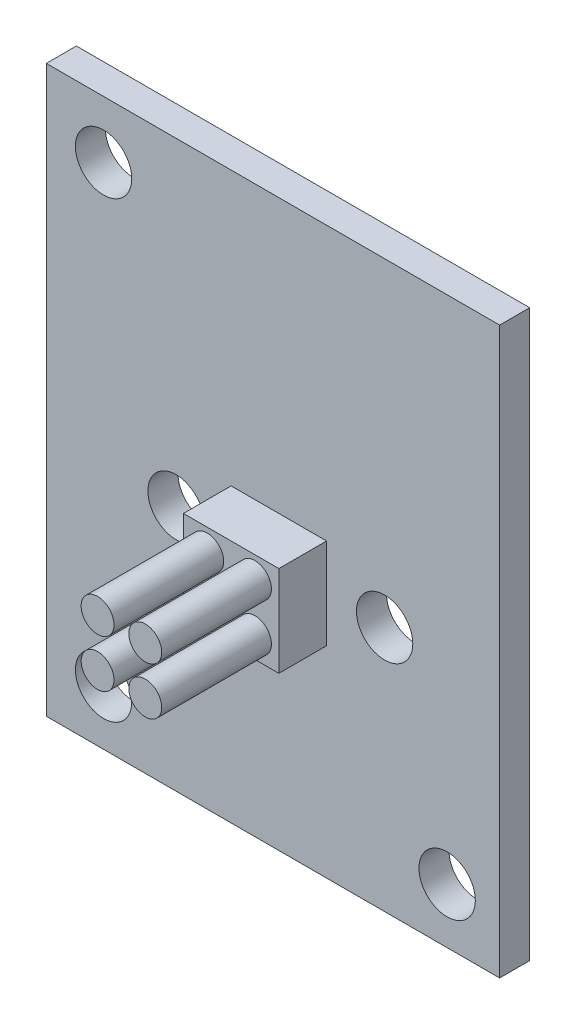
SolidWorks part; units mm, degrees
ref_plane "Front Plane" through (0, 0, 0) normal (0, 0, 1) x (1, 0, 0)
ref_plane "Top Plane" through (0, 0, 0) normal (0, 1, 0) x (1, 0, 0)
ref_plane "Right Plane" through (0, 0, 0) normal (1, 0, 0) x (0, 0, -1)
sketch "Sketch1" plane through (0, 0, 0) normal (0, 0, 1) x (1, 0, 0)
  line L0 (12.065, 30.099) -> (12.065, 35.0132) construction
  line L1 (0, 0) -> (24.13, 0)
  line L2 (0, 0) -> (0, 30.099)
  line L3 (0, 30.099) -> (24.13, 30.099)
  line L4 (24.13, 0) -> (24.13, 30.099)
  line L5 (-4.9142, -4.9142) -> (29.0442, -4.9142) construction
  line L6 (-4.9142, -4.9142) -> (-4.9142, 35.0132) construction
  line L7 (-4.9142, 35.0132) -> (29.0442, 35.0132) construction
  line L8 (29.0442, -4.9142) -> (29.0442, 35.0132) construction
  line L9 (12.065, -4.9142) -> (12.065, 0) construction
  line L10 (-4.9142, 15.0495) -> (0, 15.0495) construction
  line L11 (29.0442, 15.0495) -> (24.13, 15.0495) construction
  line L12 (0, 0) -> (-4.9142, 0) construction
  line L13 (0, 0) -> (0, -4.9142) construction
  line L14 (-4.9142, -4.9142) -> (-3.9749, -3.9749) construction
  line L15 (-1.5, 15.0495) -> (0, 15.0495) construction
  line L16 (-1.8536, -1.8536) -> (-3.9749, -3.9749) construction
  line L17 (-4.4142, -2.9142) -> (-4.9142, -2.9142) construction
  line L18 (-1.5, -1.5) -> (25.63, -1.5) construction
  line L19 (-1.5, -1.5) -> (-1.5, 31.599) construction
  line L20 (-1.5, 31.599) -> (25.63, 31.599) construction
  line L21 (25.63, -1.5) -> (25.63, 31.599) construction
  line L22 (25.63, 15.0495) -> (24.13, 15.0495) construction
  line L23 (12.065, 31.599) -> (12.065, 30.099) construction
  line L24 (12.065, -1.5) -> (12.065, 0) construction
  line L25 (-1.8536, -1.8536) -> (-1.5, -1.5)
  line L26 (13.6479, 14.3949) -> (11.1079, 11.8549) construction
  line L27 (11.1079, 11.8549) -> (13.6479, 11.8549) construction
  line L28 (11.1079, 11.8549) -> (11.1079, 14.3949) construction
  line L29 (11.1079, 14.3949) -> (13.6479, 14.3949) construction
  line L30 (13.6479, 11.8549) -> (13.6479, 14.3949) construction
  line L31 (11.1079, 14.3949) -> (13.6479, 11.8549) construction
  line L32 (14.9179, 15.5399) -> (9.8379, 10.7099) construction
  line L33 (14.9179, 10.7099) -> (9.8379, 10.7099)
  line L34 (14.9179, 10.7099) -> (14.9179, 15.5399)
  line L35 (14.9179, 15.5399) -> (9.8379, 15.5399)
  line L36 (9.8379, 10.7099) -> (9.8379, 15.5399)
  line L37 (9.8379, 15.5399) -> (14.9179, 10.7099) construction
  line L39 (5.842, 16.256) -> (23.622, 16.256)
  line L40 (5.842, 16.256) -> (5.842, 29.591)
  line L41 (5.842, 29.591) -> (23.622, 29.591)
  line L42 (23.622, 16.256) -> (23.622, 29.591)
  circle A0 centre (3.048, 2.921) radius 1.5
  circle A1 centre (21.336, 2.921) radius 1.5
  circle A2 centre (3.048, 27.051) radius 1.5
  circle A3 centre (6.908, 13.095) radius 1.5
  circle A4 centre (18.0081, 13.095) radius 1.5
  circle A5 centre (-2.9142, -2.9142) radius 1.5 construction
  circle A6 centre (27.0442, -2.9142) radius 1.5 construction
  circle A7 centre (-2.9142, 33.0132) radius 1.5 construction
  circle A8 centre (27.0442, 33.0132) radius 1.5 construction
  circle A9 centre (3.048, 2.921) radius 2 construction
  circle A10 centre (6.908, 13.095) radius 2 construction
  circle A11 centre (18.0081, 13.095) radius 2 construction
  circle A12 centre (21.336, 2.921) radius 2 construction
  circle A13 centre (3.048, 27.051) radius 2 construction
  circle A14 centre (11.1079, 14.3949) radius 0.875
  circle A15 centre (13.6479, 14.3949) radius 0.875
  circle A16 centre (11.1079, 11.8549) radius 0.875
  circle A17 centre (13.6479, 11.8549) radius 0.875
  circle A18 centre (12.3779, 13.1249) radius 3.5 construction
  circle A19 centre (12.3779, 13.1249) radius 3 construction
  arc A20 (8.8874, 13.3818) -> (8.8904, 12.8299) centre (12.3779, 13.1249) cw construction
  point P71 (12.3779, 13.1249)
  dimension "D5" = 3
  dimension "D10" = 3
  dimension "D13" = 3
  dimension "D16" = 3
  dimension "D17" = 3
  dimension "D20" = 4
  dimension "D25" = 1.75
  dimension "D26" = 7
  dimension "D27" = 0.5
  dimension "D1" = 24.13
  dimension "D2" = 30.099
  dimension "D3" = 3.048
  dimension "D4" = 2.921
  dimension "D6" = 21.336
  dimension "D7" = 2.921
  dimension "D8" = 3.048
  dimension "D9" = 27.051
  dimension "D11" = 13.095
  dimension "D12" = 6.908
  dimension "D14" = 18.0081
  dimension "D15" = 13.095
  dimension "D18" = 0.5
  dimension "D19" = 1.5
  dimension "D21" = 11.1079
  dimension "D22" = 11.8549
  dimension "D23" = 13.6479
  dimension "D24" = 14.3949
  dimension "D28" = 4.83
  dimension "D29" = 5.08
  dimension "D30" = 16.256
  dimension "D31" = 5.842
  dimension "D32" = 17.78
  dimension "D33" = 13.335
extrude "Boss-Extrude1" add sketch "Sketch1" against normal blind 1.6 contours L18 L21 L20 L19 A17 A16 A15 A14 A13 A12 A11 A10 A9 | L5 L8 L7 L6 A8 A6 A5 L19 L20 L21 L18 A7 | A10 A3 | A11 A4 | A9 A0 | A12 A1 | A13 A2 | A10 A18 A19 | L39 L42 L41 L40 region at (0.3858, 15.0495, 0) region at (12.3779, 13.1249, 0) region at (14.732, 22.9235, 0)
extrude "Boss-Extrude2" add sketch "Sketch1<19>" along normal blind 2.54 contours L36 L33 L34 L35 A17 A16 A15 A14 | A17 | A16 | A14 | A15 region at (12.3779, 13.1249, 0) region at (11.1079, 14.3949, 0) region at (13.6479, 14.3949, 0) region at (11.1079, 11.8549, 0) region at (13.6479, 11.8549, 0)
sketch "Sketch1<19>" plane through (0, 0, 0) normal (0, 0, 1) x (1, 0, 0) same geometry as "Sketch1"
extrude "Boss-Extrude3" add sketch "Sketch1<20>" along normal blind 8.38 contours A15 | A14 | A16 | A17 region at (11.1079, 14.3949, 0) region at (13.6479, 14.3949, 0) region at (11.1079, 11.8549, 0) region at (13.6479, 11.8549, 0)
sketch "Sketch1<20>" plane through (0, 0, 0) normal (0, 0, 1) x (1, 0, 0) same geometry as "Sketch1"
